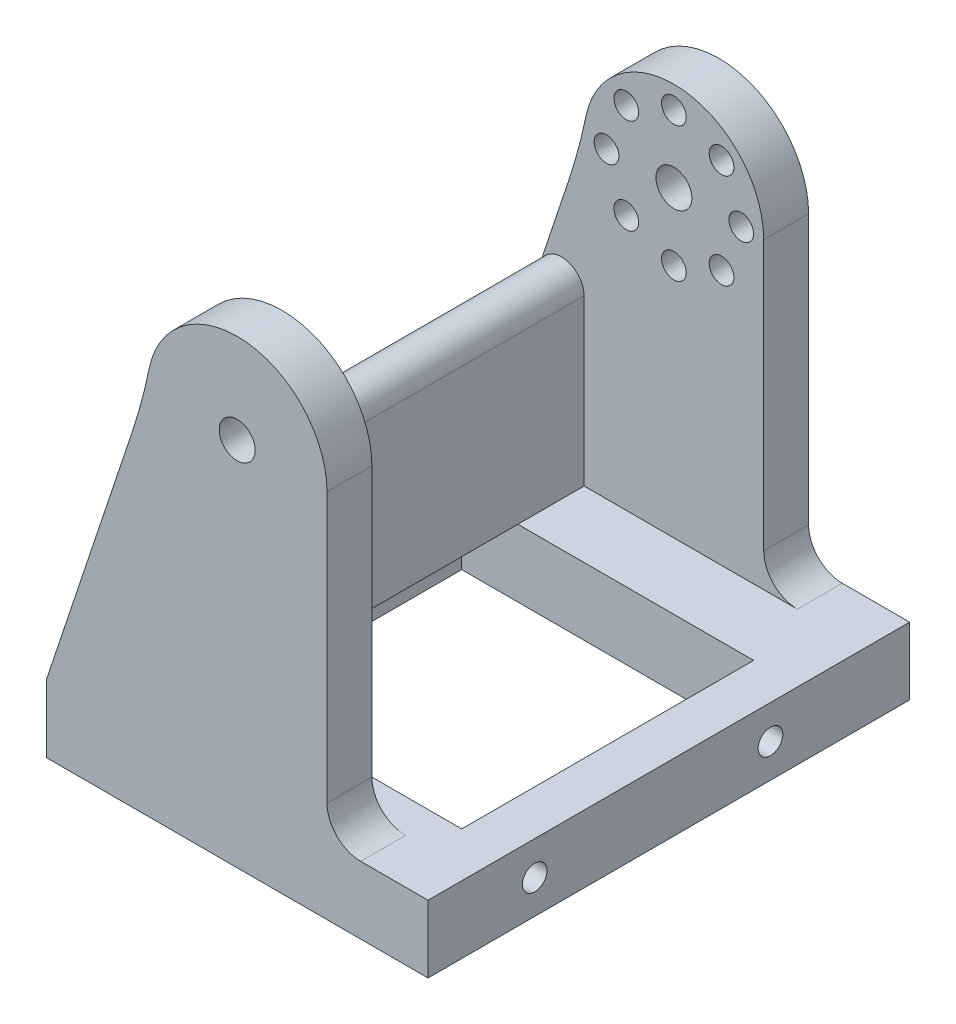
SolidWorks part; units mm, degrees
material "ABS"
ref_plane "正面" through (0, 0, 0) normal (0, 0, 1) x (1, 0, 0)
ref_plane "平面" through (0, 0, 0) normal (0, 1, 0) x (1, 0, 0)
ref_plane "右側面" through (0, 0, 0) normal (1, 0, 0) x (0, 0, -1)
sketch "ｽｹｯﾁ1" plane through (0, 0, 0) normal (0, 0, 1) x (1, 0, 0)
  line L2 (-17, -27) -> (-17, -33)
  line L3 (-17, -33) -> (17, -33)
  line L4 (17, -33) -> (17, -27)
  line L5 (0, 0) -> (0, -33) construction
  line L6 (-17, -30) -> (17, -30) construction
  line L7 (8, 0) -> (8, -24)
  line L8 (11, -27) -> (17, -27)
  line L9 (-8, 0) -> (-8, -24)
  line L10 (-11, -27) -> (-17, -27)
  arc A0 (8, 0) -> (-8, 0) centre (0, 0) ccw
  circle A1 centre (0, 0) radius 6 construction
  circle A2 centre (0, 6) radius 1.1
  circle A3 centre (4.2426, 4.2426) radius 1.1
  circle A4 centre (6, 0) radius 1.1
  circle A5 centre (4.2426, -4.2426) radius 1.1
  circle A6 centre (0, -6) radius 1.1
  circle A7 centre (-4.2426, -4.2426) radius 1.1
  circle A8 centre (-6, 0) radius 1.1
  circle A9 centre (-4.2426, 4.2426) radius 1.1
  circle A10 centre (0, 0) radius 1.6
  arc A11 (-8, -24) -> (-11, -27) centre (-11, -24) cw
  arc A12 (8, -24) -> (11, -27) centre (11, -24) ccw
  point P22 (0, 0)
  dimension "D1" = 16
  dimension "D2" = 12
  dimension "D3" = 2.2
  dimension "D8" = 3.2
  dimension "D9" = 3
  dimension "D5" = 34
  dimension "D6" = 6
  dimension "D7" = 30
  dimension "D4" = 8
extrude "ﾎﾞｽ - 押し出し1" add sketch "ｽｹｯﾁ1" along normal blind 4
sketch "ｽｹｯﾁ2" plane through (0, 0, 4) normal (0, 0, 1) x (1, 0, 0)
  line L0 (17, -27) -> (11, -27) construction
  line L1 (-17, -33) -> (-13, -33)
  line L2 (-17, -33) -> (-17, -27)
  line L3 (-17, -27) -> (-13, -27)
  line L4 (-13, -33) -> (-13, -27)
  line L5 (17, -33) -> (13, -33)
  line L6 (17, -33) -> (17, -27)
  line L7 (17, -27) -> (13, -27)
  line L8 (13, -33) -> (13, -27)
  line L9 (-11, -27) -> (-17, -27) construction
  dimension "D1" = 4
  dimension "D2" = 4
extrude "ﾎﾞｽ - 押し出し2" add sketch "ｽｹｯﾁ2" along normal blind 34.9
sketch "ｽｹｯﾁ3" plane through (0, 0, 38.9) normal (0, 0, 1) x (1, 0, 0)
  line L5 (-17, -33) -> (17, -33)
  line L6 (-17, -27) -> (-17, -33)
  line L7 (-11, -27) -> (-17, -27)
  line L8 (-11, -27) -> (-17, -27)
  line L9 (17, -33) -> (17, -27)
  line L10 (-17, -33) -> (17, -33)
  line L11 (-17, -27) -> (-17, -33)
  line L14 (17, -33) -> (17, -27)
  line L17 (-8, 0) -> (-8, -24)
  line L18 (-8, 0) -> (-8, -24)
  line L19 (8, -24) -> (8, 0)
  line L20 (8, -24) -> (8, 0)
  line L21 (17, -27) -> (11, -27)
  line L22 (17, -27) -> (11, -27)
  circle A0 centre (0, 0) radius 1.6
  arc A1 (8, 0) -> (-8, 0) centre (0, 0) ccw
  arc A2 (8, 0) -> (-8, 0) centre (0, 0) ccw
  arc A6 (-11, -27) -> (-8, -24) centre (-11, -24) ccw
  arc A7 (-11, -27) -> (-8, -24) centre (-11, -24) ccw
  arc A8 (8, -24) -> (11, -27) centre (11, -24) ccw
  arc A9 (8, -24) -> (11, -27) centre (11, -24) ccw
  dimension "D2" = 3.2
  dimension "D1" = 0
extrude "ﾎﾞｽ - 押し出し3" add sketch "ｽｹｯﾁ3" along normal blind 4
sketch "ｽｹｯﾁ4" plane through (0, -27, 0) normal (0, 1, 0) x (1, 0, 0)
  line L0 (-13, -38.9) -> (-13, -4) construction
  line L1 (13, -4) -> (-13, -4)
  line L2 (13, -4) -> (13, -9.9)
  line L3 (13, -9.9) -> (-13, -9.9)
  line L4 (-13, -4) -> (-13, -9.9)
  line L6 (13, -38.9) -> (-13, -38.9)
  line L7 (13, -38.9) -> (13, -35.9)
  line L8 (13, -35.9) -> (-13, -35.9)
  line L9 (-13, -38.9) -> (-13, -35.9)
  dimension "D1" = 5.9
  dimension "D2" = 3
extrude "ﾎﾞｽ - 押し出し4" add sketch "ｽｹｯﾁ4" against normal up to surface (6 mm away) up to face at (0, -33, 21.45)
sketch "ｽｹｯﾁ5" plane through (-8, 0, 0) normal (-1, 0, 0) x (0, 0, 1)
  line L0 (35.9, -27) -> (9.9, -27) construction
  line L1 (0, -17) -> (42.9, -17)
  line L2 (0, -17) -> (0, -27)
  line L3 (0, -27) -> (42.9, -27)
  line L4 (42.9, -17) -> (42.9, -27)
  line L5 (42.9, 0) -> (42.9, -24) construction
  line L6 (0, 0) -> (0, -24) construction
  dimension "D1" = 10
sketch "ｽｹｯﾁ6" plane through (0, 0, 0) normal (0, 0, -1) x (-1, 0, 0)
  line L0 (8, 0) -> (17, -27)
  line L1 (17, -27) -> (8, -27)
  line L2 (8, -17) -> (8, -27) construction
  line L3 (8, -27) -> (8, 0)
  line L4 (-13, -27) -> (13, -27) construction
extrude "ﾎﾞｽ - 押し出し6" add sketch "ｽｹｯﾁ6" against normal up to surface (42.9 mm away) up to face at (0, -21.5243, 42.9)
fillet "ﾌｨﾚｯﾄ1" radius 2 1 edges at (-8, 0, 21.45)
sketch "ｽｹｯﾁ7" plane through (17, 0, 0) normal (1, 0, 0) x (0, 0, -1)
  line L0 (-42.9, -30) -> (0, -30) construction
  line L1 (-42.9, -33) -> (-42.9, -27) construction
  line L2 (-22.9, -33) -> (-22.9, -27) construction
  line L3 (-42.9, -33) -> (0, -33) construction
  line L4 (-42.9, -27) -> (0, -27) construction
  line L5 (-9.9, -33) -> (-9.9, -27) construction
  circle A0 centre (-12.4, -30) radius 1.1
  circle A1 centre (-33.4, -30) radius 1.1
  dimension "D2" = 2.2
  dimension "D1" = 13
  dimension "D3" = 10.5
extrude "ｶｯﾄ - 押し出し1" cut sketch "ｽｹｯﾁ7" against normal through all
fillet "ﾌｨﾚｯﾄ2" radius 50 2 edges at (-8, 0, 40.9) (-8, 0, 2)
